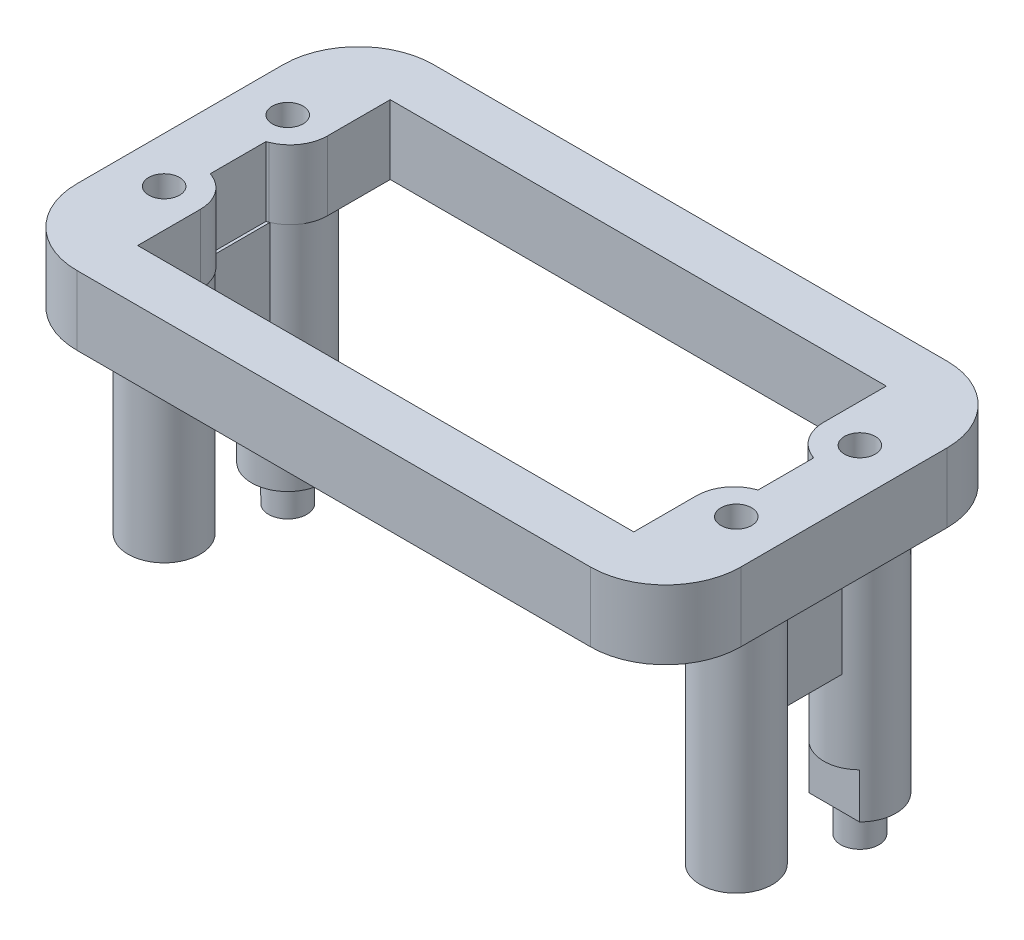
SolidWorks part; units mm, degrees
material "ABS"
ref_plane "Front Plane" through (0, 0, 0) normal (0, 0, 1) x (1, 0, 0)
ref_plane "Top Plane" through (0, 0, 0) normal (0, 1, 0) x (1, 0, 0)
ref_plane "Right Plane" through (0, 0, 0) normal (1, 0, 0) x (0, 0, -1)
sketch "Sketch1" plane through (0, 0, 0) normal (0, 1, 0) x (1, 0, 0)
  circle A0 centre (0, 0) radius 3.048
  circle A1 centre (-48.3362, 0) radius 3.048
  circle A2 centre (-48.3362, -10.4394) radius 3.048
  circle A3 centre (0, -10.4394) radius 3.048
  circle A4 centre (-48.3362, -10.4394) radius 1.2319
  circle A5 centre (-48.3362, 0) radius 1.2319
  circle A6 centre (0, 0) radius 1.2319
  circle A7 centre (0, -10.4394) radius 1.2319
  dimension "D1" = 6.096
  dimension "D2" = 10.4394
  dimension "D3" = 10.4394
  dimension "D4" = 48.3362
  dimension "D5" = 2.4638
extrude "Boss-Extrude1" add sketch "Sketch1" against normal blind 25.4 contours A7 | A3 A7 | A0 A6 | A6 | A4 | A2 A4 | A1 A5 | A5 region at (-2.9618, 0, 0) region at (-51.298, 0, 0) region at (-51.298, 0, 10.4394) region at (-2.9618, 0, 10.4394) region at (-48.3362, 0, 10.4394) region at (-48.3362, 0, 0) region at (0, 0, 0) region at (0, 0, 10.4394)
sketch "Sketch2" plane through (0, 0, 0) normal (0, 1, 0) x (1, 0, 0)
  line L1 (-52.2097, 9.8425) -> (3.8735, 9.8425)
  line L2 (-52.2097, 9.8425) -> (-52.2097, -20.2819)
  line L3 (-52.2097, -20.2819) -> (3.8735, -20.2819)
  line L4 (3.8735, 9.8425) -> (3.8735, -20.2819)
  line L5 (-48.3362, -5.2197) -> (0, -5.2197) construction
  line L7 (0, -2.8575) -> (3.8735, -2.8575) construction
  line L8 (-48.3362, -2.8575) -> (-52.2097, -2.8575) construction
  line L9 (-45.4787, -10.4394) -> (-45.1231, -10.4394) construction
  line L10 (-3.2131, -15.8877) -> (-45.1231, -15.8877)
  line L11 (-3.2131, -15.8877) -> (-3.2131, -7.6454)
  line L12 (-3.2131, 5.4483) -> (-45.1231, 5.4483)
  line L13 (-45.1231, -15.8877) -> (-45.1231, -7.6454)
  line L14 (-3.2131, -15.8877) -> (-45.1231, 5.4483) construction
  line L15 (-3.2131, 5.4483) -> (-45.1231, -15.8877) construction
  line L16 (-2.8575, -10.4394) -> (-3.2131, -10.4394) construction
  line L17 (-24.1681, 5.4483) -> (-24.1681, -15.8877) construction
  line L18 (-47.3075, -2.794) -> (-45.1231, -2.794)
  line L19 (-47.3075, -2.794) -> (-47.3075, -7.6454)
  line L20 (-47.3075, -7.6454) -> (-45.1231, -7.6454)
  line L21 (-3.2131, -2.794) -> (-3.2131, 5.4483)
  line L22 (-1.0287, -2.794) -> (-3.2131, -2.794)
  line L23 (-1.0287, -7.6454) -> (-3.2131, -7.6454)
  line L24 (-1.0287, -2.794) -> (-1.0287, -7.6454)
  line L25 (-47.3075, -2.794) -> (-45.1231, -2.794)
  line L26 (-45.1231, -2.794) -> (-45.1231, 5.4483)
  point P14 (-24.1681, -5.2197)
  dimension "D1" = 30.1244
  dimension "D2" = 56.0832
  dimension "D3" = 41.91
  dimension "D4" = 21.336
  dimension "D5" = 2.1844
  dimension "D6" = 4.8514
extrude "Boss-Extrude3" add sketch "Sketch2" against normal blind 5.842 contours L4 L1 L2 L3 L18 L26 L12 L21 L22 L24 L23 L11 L10 L13 L20 L19 region at (-24.1681, 0, -9.2059)
sketch "Sketch4" plane through (0, -25.4, 0) normal (0, -1, 0) x (1, 0, 0)
  circle A0 centre (0, 0) radius 1.2319
  circle A1 centre (0, 10.4394) radius 1.2319
  circle A2 centre (-48.3362, 10.4394) radius 1.2319
  circle A3 centre (-48.3362, 0) radius 1.2319
  dimension "D1" = 2.4638
sketch "Sketch5" plane through (0, 0, 0) normal (0, 1, 0) x (1, 0, 0)
  circle A0 centre (0, 0) radius 1.2319
  circle A1 centre (0, -10.4394) radius 1.2319
  circle A2 centre (-48.3362, -10.4394) radius 1.2319
  circle A3 centre (-48.3362, 0) radius 1.2319
  dimension "D1" = 2.4638
fillet "Fillet1" radius 3.175 4 edges at (-3.2131, -2.921, 7.6454) (-3.2131, -2.921, 2.794) (-45.1231, -2.921, 2.794) (-45.1231, -2.921, 7.6454)
fillet "Fillet3" radius 6.35 4 edges at (-52.2097, -2.921, -9.8425) (3.8735, -2.921, -9.8425) (3.8735, -2.921, 20.2819) (-52.2097, -2.921, 20.2819)
ref_plane "Plane1" through (0, 0, 0) normal (1, 0, 0) x (0, 0, -1)
sketch "Sketch6" plane through (0, 0, 0) normal (1, 0, 0) x (0, 0, -1)
  line L0 (-5.2197, -5.842) -> (-5.2197, -27.2461) construction
  line L1 (3.4925, -5.842) -> (-13.9319, -5.842) construction
  line L2 (-13.4874, -5.842) -> (-7.3914, -5.842) construction
  line L3 (-8.1407, -5.842) -> (-2.2987, -5.842)
  line L4 (-8.1407, -5.842) -> (-8.1407, -14.732)
  line L5 (-8.1407, -14.732) -> (-2.2987, -14.732)
  line L6 (-2.2987, -5.842) -> (-2.2987, -14.732)
  dimension "D1" = 5.842
  dimension "D2" = 8.89
extrude "Boss-Extrude4" add sketch "Sketch6" along normal mid plane 2.54
ref_plane "Plane2" through (-48.3362, 0, 0) normal (-1, 0, 0) x (0, 0, 1)
sketch "Sketch7" plane through (-48.3362, 0, 0) normal (-1, 0, 0) x (0, 0, 1)
  line L0 (5.2197, -5.842) -> (5.2197, -27.3012) construction
  line L1 (-3.4925, -5.842) -> (13.9319, -5.842) construction
  line L2 (-3.048, -5.842) -> (3.048, -5.842) construction
  line L3 (2.2987, -5.842) -> (8.1407, -5.842)
  line L4 (2.2987, -5.842) -> (2.2987, -14.732)
  line L5 (2.2987, -14.732) -> (8.1407, -14.732)
  line L6 (8.1407, -5.842) -> (8.1407, -14.732)
  dimension "D1" = 5.842
  dimension "D2" = 8.89
extrude "Boss-Extrude5" add sketch "Sketch7" along normal mid plane 2.54
sketch "Sketch16" plane through (0, -25.4, 0) normal (0, -1, 0) x (1, 0, 0)
  circle A0 centre (0, 0) radius 1.6129
  circle A1 centre (-48.3362, 0) radius 1.6129
  dimension "D1" = 3.2258
extrude "Boss-Extrude6" add sketch "Sketch16" along normal blind 3.0226
sketch "Sketch17" plane through (0, 0, 0) normal (0, 1, 0) x (1, 0, 0)
  line L0 (-54.8134, -5.2197) -> (9.031, -5.2197) construction
  line L1 (-24.1681, 13.053) -> (-24.1681, -25.2536) construction
  line L4 (-3.2131, 5.4483) -> (-45.1231, 5.4483) construction
  line L5 (-3.2131, -15.8877) -> (-45.1231, -15.8877) construction
  line L6 (-45.1231, 0.1536) -> (-45.1231, 5.4483) construction
  line L7 (-3.2131, 0.1536) -> (-3.2131, 5.4483) construction
  circle A0 centre (-48.3362, -10.4394) radius 1.4224
  circle A1 centre (-48.3362, 0) radius 1.4224
  circle A2 centre (0, 0) radius 1.4224
  circle A3 centre (0, -10.4394) radius 1.4224
  dimension "D1" = 10.4394
  dimension "D2" = 2.8448
  dimension "D3" = 48.3362
sketch "Sketch19" plane through (0, 0, 0) normal (0, 1, 0) x (1, 0, 0)
  circle A0 centre (-48.3362, -10.4394) radius 1.3017
  circle A1 centre (0, -10.4394) radius 1.3018
  dimension "D1" = 2.6035
extrude "Cut-Extrude1" cut sketch "Sketch19" against normal through all
sketch "Sketch20" plane through (0, 0, 0) normal (0, 1, 0) x (1, 0, 0)
  circle A0 centre (0, 0) radius 1.3017
  circle A1 centre (-48.3362, 0) radius 1.3017
  dimension "D1" = 2.6035
extrude "Cut-Extrude2" cut sketch "Sketch20" against normal through all
sketch "Sketch21" plane through (0, -28.4226, 0) normal (0, -1, 0) x (1, 0, 0)
  circle A0 centre (-48.3362, 0) radius 1.3017
  circle A1 centre (-48.3362, 0) radius 0.635
  circle A2 centre (0, 0) radius 1.3017
  circle A3 centre (0, 0) radius 0.635
  dimension "D1" = 2.6035
  dimension "D2" = 1.27
extrude "Boss-Extrude7" add sketch "Sketch21" against normal blind 12.3825
sketch "Sketch24" plane through (0, -25.4, 0) normal (0, -1, 0) x (1, 0, 0)
  line L0 (-1.27, 5.2197) -> (1.27, 5.2197) construction
  line L1 (-1.27, 7.6686) -> (-1.27, 2.7708) construction
  line L2 (1.27, 2.7708) -> (1.27, 7.6686) construction
  line L3 (0, 8.2677) -> (0, 2.1717) construction
  line L5 (3.4686, 8.2677) -> (-3.4686, 8.2677)
  line L6 (3.4686, 8.2677) -> (3.4686, 2.1717)
  line L7 (3.4686, 2.1717) -> (-3.4686, 2.1717)
  line L8 (-3.4686, 8.2677) -> (-3.4686, 2.1717)
  line L9 (3.4686, 8.2677) -> (-3.4686, 2.1717) construction
  line L10 (3.4686, 2.1717) -> (-3.4686, 8.2677) construction
  point P6 (0, 5.2197)
  point P10 (0, 5.2197)
  dimension "D1" = 6.096
extrude "Cut-Extrude4" cut sketch "Sketch24" against normal blind 3.81
